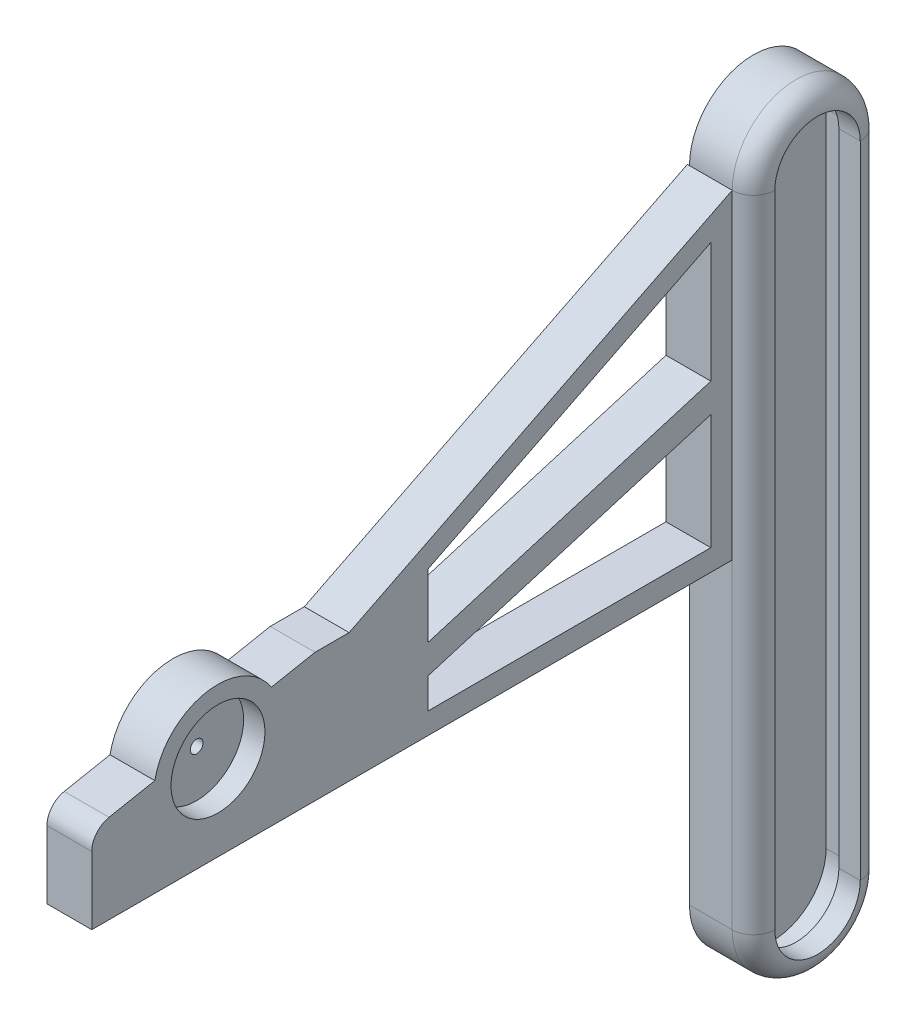
SolidWorks part; units mm, degrees
ref_plane "Front Plane" through (0, 0, 0) normal (0, 0, 1) x (1, 0, 0)
ref_plane "Top Plane" through (0, 0, 0) normal (0, 1, 0) x (1, 0, 0)
ref_plane "Right Plane" through (0, 0, 0) normal (1, 0, 0) x (0, 0, -1)
sketch "Sketch1" plane through (0, 0, 0) normal (1, 0, 0) x (0, 0, -1)
  line L0 (-20, 0) -> (-20, 300)
  line L1 (-30, 300) -> (-30, 0)
  line L2 (30, 0) -> (30, 300)
  line L3 (20, 300) -> (20, 0)
  arc A0 (30, 300) -> (-30, 300) centre (0, 300) ccw
  arc A1 (-30, 0) -> (30, 0) centre (0, 0) ccw
  arc A2 (20, 300) -> (-20, 300) centre (0, 300) ccw
  arc A3 (-20, 0) -> (20, 0) centre (0, 0) ccw
  dimension "D1" = 300
extrude "Boss-Extrude3" add sketch "Sketch1" along normal blind 10 contours A2 L0 A3 L3
extrude "Boss-Extrude4" add sketch "Sketch1<5>" along normal blind 30
sketch "Sketch1<5>" plane through (0, 0, 0) normal (1, 0, 0) x (0, 0, -1) same geometry as "Sketch1"
sketch "Sketch2" plane through (10, 0, 0) normal (1, 0, 0) x (0, 0, -1)
  line L2 (-25, 0) -> (-25, 300)
  line L3 (25, 300) -> (25, 0)
  arc A2 (25, 300) -> (-25, 300) centre (0, 300) ccw
  arc A3 (-25, 0) -> (25, 0) centre (0, 0) ccw
extrude "Cut-Extrude1" cut sketch "Sketch2" along normal blind 10 and the other way blind 1
fillet "Fillet1" radius 10 4 edges at (30, -30, 0) (30, 150, 30) (30, 150, -30) (30, 330, 0)
sketch "Sketch4" plane through (20, 0, 0) normal (-1, 0, 0) x (0, 0, 1)
  line L16 (30, 300) -> (30, 150)
  line L17 (30, 0) -> (30, 300) construction
  line L18 (30, 150) -> (330, 150)
  line L19 (209.4454, 210.2773) -> (30, 300)
  line L23 (209.4454, 210.2773) -> (225.4454, 210.2773)
  line L24 (330, 190) -> (330, 150)
  line L25 (225.4454, 210.2773) -> (245.8545, 206.3192)
  line L26 (300.4761, 195.7259) -> (330, 190)
  arc A0 (300.4761, 195.7259) -> (245.8545, 206.3192) centre (271.0276, 190) ccw
  dimension "D1" = 16
  dimension "D2" = 40
  dimension "D4" = 300
extrude "Boss-Extrude5" add sketch "Sketch4" along normal blind 21 contours L19 L16 L18 L24 L26 A0 L25 L23
sketch "Sketch6" plane through (20, 0, 0) normal (1, 0, 0) x (0, 0, -1)
  line L0 (-40, 160) -> (-40, 213.9897)
  line L2 (-172.5349, 160) -> (-40, 160)
  line L3 (-30, 300) -> (-30, 150) construction
  line L4 (-30, 150) -> (-330, 150) construction
  line L6 (-40, 283.8197) -> (-172.5349, 217.5522)
  line L8 (-209.4454, 210.2773) -> (-30, 300) construction
  line L9 (-172.5349, 160) -> (-172.5349, 174.2292)
  line L10 (-172.5349, 187.8016) -> (-172.5349, 217.5522)
  line L11 (-172.5349, 187.8016) -> (-40, 227.5621)
  line L12 (-172.5349, 174.2292) -> (-40, 213.9897)
  line L13 (-40, 227.5621) -> (-40, 283.8197)
  dimension "D1" = 10
  dimension "D2" = 10
  dimension "D3" = 10
  dimension "D4" = 13
extrude "Cut-Extrude2" cut sketch "Sketch6" against normal blind 21
fillet "Fillet2" radius 10 1 edges at (9.5, 190, 330)
sketch "Sketch15" plane through (-1, 0, 0) normal (-1, 0, 0) x (0, 0, 1)
  circle A0 centre (270.8771, 189.7852) radius 3
extrude "Cut-Extrude3" cut sketch "Sketch15" against normal blind 21
sketch "Sketch16" plane through (20, 0, 0) normal (1, 0, 0) x (0, 0, -1)
  circle A0 centre (-270.8771, 189.7852) radius 22
extrude "Cut-Extrude4" cut sketch "Sketch16" against normal blind 10
